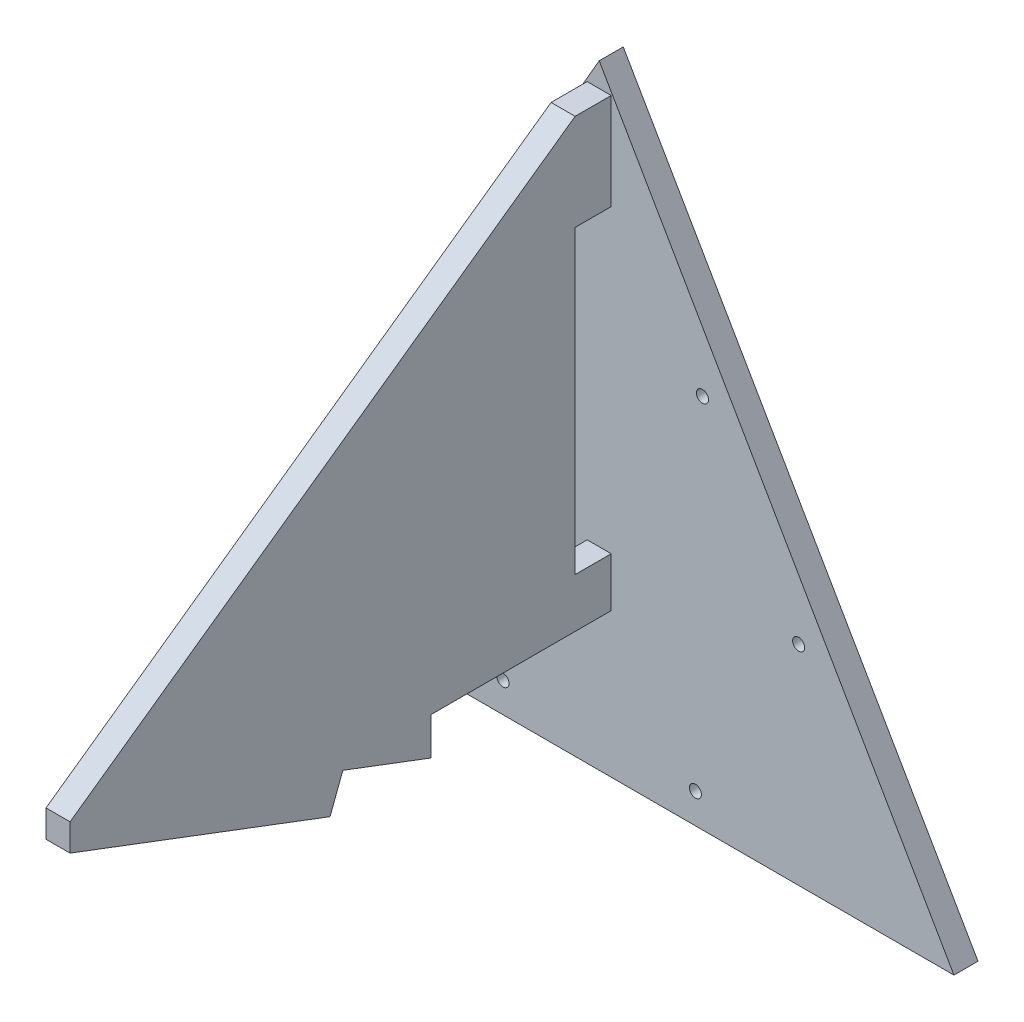
SolidWorks part; units mm, degrees
ref_plane "Front Plane" through (0, 0, 0) normal (0, 0, 1) x (1, 0, 0)
ref_plane "Top Plane" through (0, 0, 0) normal (0, 1, 0) x (1, 0, 0)
ref_plane "Right Plane" through (0, 0, 0) normal (1, 0, 0) x (0, 0, -1)
sketch "Sketch1" plane through (0, 0, 0) normal (0, 0, 1) x (1, 0, 0)
  line L0 (0, 34.0637) -> (-29.5, -17.0318)
  line L1 (-29.5, -17.0318) -> (29.5, -17.0318)
  line L2 (29.5, -17.0318) -> (0, 34.0637)
  line L3 (0, 34.0637) -> (0, -17.0318) construction
  line L4 (-14.75, 8.5159) -> (29.5, -17.0318) construction
  point P4 (0, 0)
  point P5 (0, 0)
  dimension "D1" = 59
extrude "Boss-Extrude1" add sketch "Sketch1" along normal blind 2
sketch "Sketch2" plane through (0, 0, 0) normal (1, 0, 0) x (0, 0, -1)
  line L0 (0, 0) -> (50000, 0) construction
  line L1 (-2, -0.9363) -> (-2, -5.0318)
  line L2 (-2, -17.0318) -> (-2, 34.0637) construction
  line L3 (-2, -5.0318) -> (-17, -5.0318)
  line L4 (-17, -5.0318) -> (-17, -8.1469)
  line L5 (-17, -8.1469) -> (-24.3194, -5.3766)
  line L6 (-24.3194, -5.3766) -> (-25.3813, -8.1823)
  line L7 (-25.3813, -8.1823) -> (-47, 0)
  line L8 (-2, 32.0637) -> (-5, 32.0637)
  line L9 (-5, 32.0637) -> (-47, 2.2599)
  line L10 (-47, 2.2599) -> (-47, 0)
  line L11 (-2, 32.0637) -> (-2, 24.0637)
  line L12 (-2, 24.0637) -> (-5, 24.0637)
  line L13 (-5, 24.0637) -> (-5, -0.9363)
  line L14 (-5, -0.9363) -> (-2, -0.9363)
  dimension "D1" = 15
  dimension "D2" = 3
  dimension "D3" = 45
  dimension "D4" = 12
  dimension "D5" = 25
  dimension "D6" = 3
  dimension "D7" = 35.36
  dimension "D8" = 2
  dimension "D9" = 8
  dimension "D10" = 3
  dimension "D11" = 25
extrude "Boss-Extrude2" add sketch "Sketch2" along normal mid plane 2
sketch "Sketch3" plane through (0, 0, 2) normal (0, 0, 1) x (1, 0, 0)
  line L0 (0, -1017.0318) -> (0, 48982.9682) construction
  line L1 (-29.5, -17.0318) -> (29.5, -17.0318) construction
  circle A0 centre (-8, -14.5318) radius 0.5
  circle A1 centre (8, -14.5318) radius 0.5
  point P5 (0, -17.0318)
  dimension "D1" = 1
  dimension "D2" = 8
  dimension "D3" = 2.5
extrude "Cut-Extrude1" cut sketch "Sketch3" against normal through all
ref_axis "Axis1" through (0, 0, -2.35) along (0, 0, 1)
pattern_circular "CirPattern1" count 3 over 360 about axis through (0, 0, -2.35) along (0, 0, 1) of "Cut-Extrude1"
